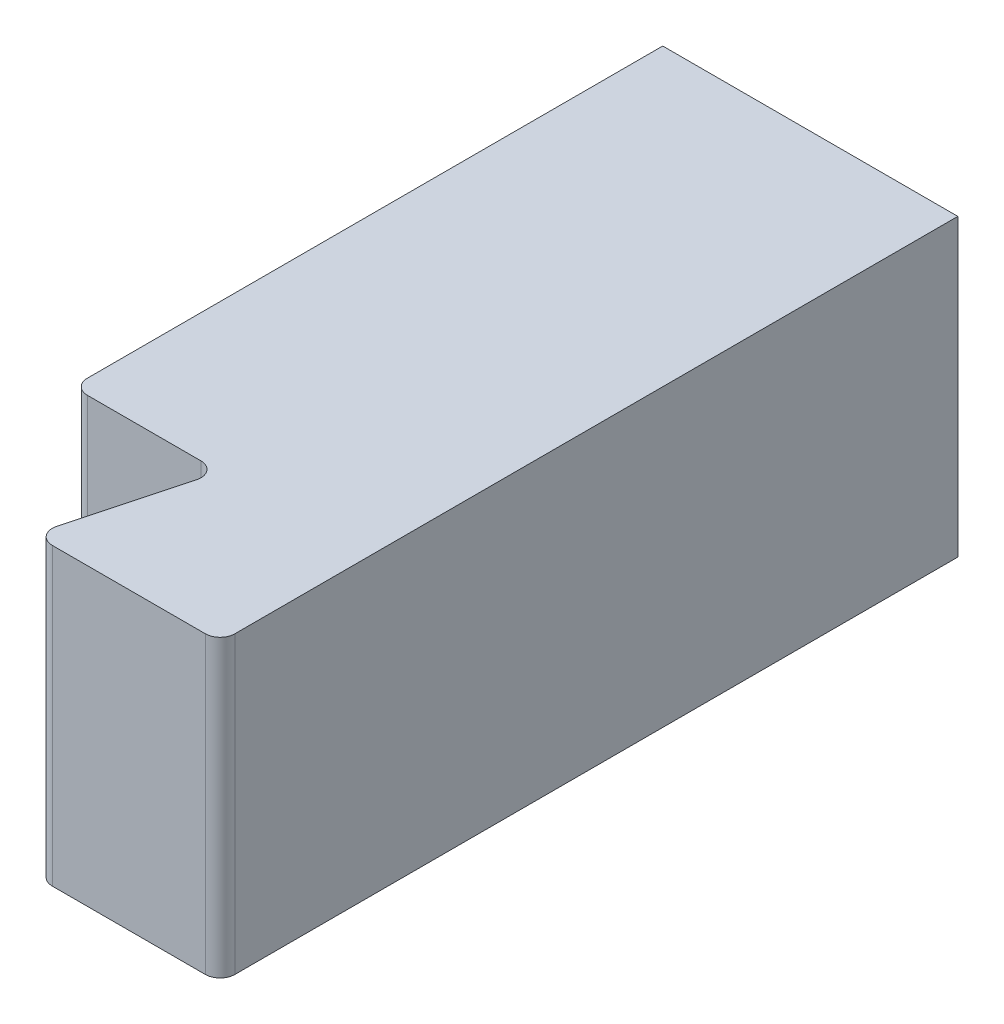
SolidWorks part; units mm, degrees
ref_plane "Top" through (0, 0, 0) normal (0, 0, 1) x (1, 0, 0)
ref_plane "Front" through (0, 0, 0) normal (0, 1, 0) x (1, 0, 0)
ref_plane "Right" through (0, 0, 0) normal (1, 0, 0) x (0, 0, -1)
sketch "Profile Sketch" plane through (-14.3347, 0, -24.6701) normal (0, 1, 0) x (-1, 0, 0)
  line L0 (5, 20) -> (5, 0)
  line L1 (5, 0) -> (-5, 0)
  line L2 (-5, 0) -> (-5, 25)
  line L3 (-5, 25) -> (1.3397, 25)
  line L4 (1.3397, 25) -> (0, 20)
  line L5 (0, 20) -> (5, 20)
  line L7 (0, 20) -> (0, 0) construction
  dimension "D1" = 5
  dimension "Width" = 10
  dimension "PCB Height" = 20
  dimension "D4" = 75
extrude "Length Extrude" add sketch "Profile Sketch" along normal mid plane 10
fillet "Edge Fillets" radius 0.5 4 edges at (-15.6744, 0, 0.3299) (-14.3347, 0, -4.6701) (-9.3347, 0, 0.3299) (-19.3347, 0, -4.6701)
sketch "Magneet Slot Sketch" plane through (0, 0, -24.6701) normal (0, 0, -1) x (-1, 0, 0)
  line L0 (14.3347, -5) -> (14.3347, 0) construction
  line L1 (9.3347, -5) -> (19.3347, -5) construction
  line L2 (14.7094, -3.2076) -> (14.5597, -3.0819)
  line L3 (13.9599, -3.2076) -> (14.1097, -3.0819)
  line L4 (11.3695, -1.2792) -> (11.5532, -1.3461)
  line L5 (11.7442, -1.9283) -> (11.7782, -1.7358)
  line L6 (11.7442, 1.9283) -> (11.7782, 1.7358)
  line L7 (11.3695, 1.2792) -> (11.5532, 1.3461)
  line L8 (14.7094, 3.2076) -> (14.5597, 3.0819)
  line L9 (13.9599, 3.2076) -> (14.1097, 3.0819)
  line L10 (17.2999, 1.2792) -> (17.1162, 1.3461)
  line L11 (16.9251, 1.9283) -> (16.8912, 1.7358)
  line L12 (16.9251, -1.9283) -> (16.8912, -1.7358)
  line L13 (17.2999, -1.2792) -> (17.1162, -1.3461)
  line L14 (9.3347, 0) -> (14.3347, 0) construction
  line L15 (9.3347, 5) -> (9.3347, -5) construction
  arc A0 (15.0044, -3.2824) -> (16.8425, -2.2212) centre (14.3347, 0) ccw
  arc A1 (15.0044, -3.2824) -> (14.7094, -3.2076) centre (14.9344, -2.9394) cw
  arc A2 (14.5597, -3.0819) -> (14.1097, -3.0819) centre (14.3347, -3.35) ccw
  arc A3 (13.665, -3.2824) -> (13.9599, -3.2076) centre (13.735, -2.9394) ccw
  circle A4 centre (14.3347, 0) radius 3 construction
  arc A5 (11.1572, -1.0612) -> (11.3695, -1.2792) centre (11.4892, -0.9503) ccw
  arc A6 (11.7782, -1.7358) -> (11.5532, -1.3461) centre (11.4335, -1.675) ccw
  arc A7 (11.8269, -2.2212) -> (11.7442, -1.9283) centre (12.0889, -1.9891) cw
  arc A8 (11.8269, 2.2212) -> (11.7442, 1.9283) centre (12.0889, 1.9891) ccw
  arc A9 (11.5532, 1.3461) -> (11.7782, 1.7358) centre (11.4335, 1.675) ccw
  arc A10 (11.1572, 1.0612) -> (11.3695, 1.2792) centre (11.4892, 0.9503) cw
  arc A11 (15.0044, 3.2824) -> (14.7094, 3.2076) centre (14.9344, 2.9394) ccw
  arc A12 (14.1097, 3.0819) -> (14.5597, 3.0819) centre (14.3347, 3.35) ccw
  arc A13 (13.665, 3.2824) -> (13.9599, 3.2076) centre (13.735, 2.9394) cw
  arc A14 (17.5122, 1.0612) -> (17.2999, 1.2792) centre (17.1802, 0.9503) ccw
  arc A15 (16.8912, 1.7358) -> (17.1162, 1.3461) centre (17.2359, 1.675) ccw
  arc A16 (16.8425, 2.2212) -> (16.9251, 1.9283) centre (16.5805, 1.9891) cw
  arc A17 (16.8425, -2.2212) -> (16.9251, -1.9283) centre (16.5805, -1.9891) ccw
  arc A18 (17.1162, -1.3461) -> (16.8912, -1.7358) centre (17.2359, -1.675) ccw
  arc A19 (17.5122, -1.0612) -> (17.2999, -1.2792) centre (17.1802, -0.9503) cw
  arc A20 (17.5122, -1.0612) -> (17.5122, 1.0612) centre (14.3347, 0) ccw
  arc A21 (16.8425, 2.2212) -> (15.0044, 3.2824) centre (14.3347, 0) ccw
  arc A22 (13.665, 3.2824) -> (11.8269, 2.2212) centre (14.3347, 0) ccw
  arc A23 (11.1572, 1.0612) -> (11.1572, -1.0612) centre (14.3347, 0) ccw
  arc A24 (11.8269, -2.2212) -> (13.665, -3.2824) centre (14.3347, 0) ccw
  dimension "D2" = 130
  dimension "D3" = 6
  dimension "D4" = 0.35
  dimension "D5" = 0.35
  dimension "D6" = 6
extrude "Magnet Slot Cut" cut sketch "Magneet Slot Sketch" against normal blind 2
other "Magnet Holes Fill Pattern" [suppressed] parameters "D5"=0, "D6"=0, "D4"=30, "D9"=5, "D3"=0, "D7"=3, "D8"=21
